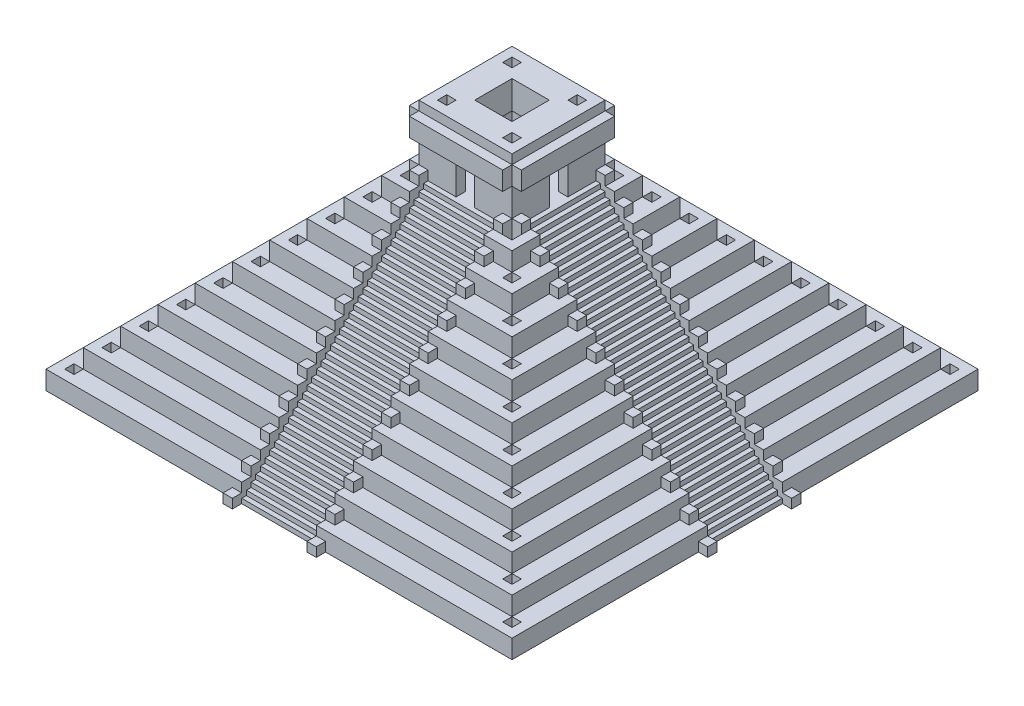
SolidWorks part; units mm, degrees
ref_plane "Ebene vorne" through (0, 0, 0) normal (0, 0, 1) x (1, 0, 0)
ref_plane "Ebene oben" through (0, 0, 0) normal (0, 1, 0) x (1, 0, 0)
ref_plane "Ebene rechts" through (0, 0, 0) normal (1, 0, 0) x (0, 0, -1)
ref_axis "Achse1" through (0, -1.35, 0) along (0, 1, 0)
sketch "Skizze1" plane through (0, 0, 0) normal (0, 1, 0) x (1, 0, 0)
  line L1 (-25, -25) -> (25, -25)
  line L2 (-25, -25) -> (-25, 25)
  line L3 (-25, 25) -> (25, 25)
  line L4 (25, -25) -> (25, 25)
  line L5 (-25, -25) -> (25, 25) construction
  line L6 (-25, 25) -> (25, -25) construction
  line L7 (-20, 20) -> (20, 20)
  line L8 (-20, 20) -> (-20, -20)
  line L9 (-20, -20) -> (20, -20)
  line L10 (20, 20) -> (20, -20)
  dimension "D1" = 50
  dimension "D2" = 5
extrude "Aufsatz-Linear austragen1" add sketch "Skizze1" along normal blind 2
sketch "Skizze2" plane through (0, 2, 0) normal (0, 1, 0) x (1, 0, 0)
  line L8 (-23, -23) -> (23, -23)
  line L9 (23, -23) -> (23, 23)
  line L10 (23, 23) -> (-23, 23)
  line L11 (-23, 23) -> (-23, -23)
  line L12 (-23, -23) -> (23, -23)
  line L13 (23, -23) -> (23, 23)
  line L14 (23, 23) -> (-23, 23)
  line L15 (-23, 23) -> (-23, -23)
  line L20 (18, -18) -> (18, 18)
  line L21 (-18, -18) -> (18, -18)
  line L22 (18, 18) -> (-18, 18)
  line L23 (-18, 18) -> (-18, -18)
  line L24 (18, -18) -> (18, 18)
  line L25 (-18, -18) -> (18, -18)
  line L26 (18, 18) -> (-18, 18)
  line L27 (-18, 18) -> (-18, -18)
  dimension "D1" = 2
  dimension "D2" = 2
extrude "Aufsatz-Linear austragen2" add sketch "Skizze2" along normal blind 2
sketch "Skizze3" plane through (0, 4, 0) normal (0, 1, 0) x (1, 0, 0)
  line L8 (-21, 21) -> (-21, -21)
  line L9 (-21, -21) -> (21, -21)
  line L10 (21, -21) -> (21, 21)
  line L11 (21, 21) -> (-21, 21)
  line L12 (-21, 21) -> (-21, -21)
  line L13 (-21, -21) -> (21, -21)
  line L14 (21, -21) -> (21, 21)
  line L15 (21, 21) -> (-21, 21)
  line L20 (-16, -16) -> (16, -16)
  line L21 (16, -16) -> (16, 16)
  line L22 (16, 16) -> (-16, 16)
  line L23 (-16, 16) -> (-16, -16)
  line L24 (-16, -16) -> (16, -16)
  line L25 (16, -16) -> (16, 16)
  line L26 (16, 16) -> (-16, 16)
  line L27 (-16, 16) -> (-16, -16)
  dimension "D1" = 2
  dimension "D2" = 2
extrude "Aufsatz-Linear austragen3" add sketch "Skizze3" along normal blind 2
sketch "Skizze4" plane through (0, 6, 0) normal (0, 1, 0) x (1, 0, 0)
  line L8 (19, 19) -> (-19, 19)
  line L9 (-19, 19) -> (-19, -19)
  line L10 (-19, -19) -> (19, -19)
  line L11 (19, -19) -> (19, 19)
  line L12 (19, 19) -> (-19, 19)
  line L13 (-19, 19) -> (-19, -19)
  line L14 (-19, -19) -> (19, -19)
  line L15 (19, -19) -> (19, 19)
  line L20 (14, -14) -> (14, 14)
  line L21 (-14, -14) -> (14, -14)
  line L22 (14, 14) -> (-14, 14)
  line L23 (-14, 14) -> (-14, -14)
  line L24 (14, -14) -> (14, 14)
  line L25 (-14, -14) -> (14, -14)
  line L26 (14, 14) -> (-14, 14)
  line L27 (-14, 14) -> (-14, -14)
  dimension "D1" = 2
  dimension "D2" = 2
extrude "Aufsatz-Linear austragen4" add sketch "Skizze4" along normal blind 2
sketch "Skizze5" plane through (0, 8, 0) normal (0, 1, 0) x (1, 0, 0)
  line L8 (17, -17) -> (17, 17)
  line L9 (17, 17) -> (-17, 17)
  line L10 (-17, 17) -> (-17, -17)
  line L11 (-17, -17) -> (17, -17)
  line L12 (17, -17) -> (17, 17)
  line L13 (17, 17) -> (-17, 17)
  line L14 (-17, 17) -> (-17, -17)
  line L15 (-17, -17) -> (17, -17)
  line L20 (-12, -12) -> (12, -12)
  line L21 (12, -12) -> (12, 12)
  line L22 (12, 12) -> (-12, 12)
  line L23 (-12, 12) -> (-12, -12)
  line L24 (-12, -12) -> (12, -12)
  line L25 (12, -12) -> (12, 12)
  line L26 (12, 12) -> (-12, 12)
  line L27 (-12, 12) -> (-12, -12)
  dimension "D1" = 2
  dimension "D2" = 2
extrude "Aufsatz-Linear austragen5" add sketch "Skizze5" along normal blind 2
sketch "Skizze6" plane through (0, 10, 0) normal (0, 1, 0) x (1, 0, 0)
  line L8 (-15, -15) -> (15, -15)
  line L9 (15, -15) -> (15, 15)
  line L10 (15, 15) -> (-15, 15)
  line L11 (-15, 15) -> (-15, -15)
  line L12 (-15, -15) -> (15, -15)
  line L13 (15, -15) -> (15, 15)
  line L14 (15, 15) -> (-15, 15)
  line L15 (-15, 15) -> (-15, -15)
  line L20 (-10, -10) -> (10, -10)
  line L21 (10, -10) -> (10, 10)
  line L22 (10, 10) -> (-10, 10)
  line L23 (-10, 10) -> (-10, -10)
  line L24 (-10, -10) -> (10, -10)
  line L25 (10, -10) -> (10, 10)
  line L26 (10, 10) -> (-10, 10)
  line L27 (-10, 10) -> (-10, -10)
  dimension "D1" = 2
  dimension "D2" = 2
extrude "Aufsatz-Linear austragen6" add sketch "Skizze6" along normal blind 2
sketch "Skizze7" plane through (0, 12, 0) normal (0, 1, 0) x (1, 0, 0)
  line L8 (-13, 13) -> (-13, -13)
  line L9 (-13, -13) -> (13, -13)
  line L10 (13, -13) -> (13, 13)
  line L11 (13, 13) -> (-13, 13)
  line L12 (-13, 13) -> (-13, -13)
  line L13 (-13, -13) -> (13, -13)
  line L14 (13, -13) -> (13, 13)
  line L15 (13, 13) -> (-13, 13)
  line L20 (8, -8) -> (8, 8)
  line L21 (-8, -8) -> (8, -8)
  line L22 (8, 8) -> (-8, 8)
  line L23 (-8, 8) -> (-8, -8)
  line L24 (8, -8) -> (8, 8)
  line L25 (-8, -8) -> (8, -8)
  line L26 (8, 8) -> (-8, 8)
  line L27 (-8, 8) -> (-8, -8)
  dimension "D1" = 2
  dimension "D2" = 2
extrude "Aufsatz-Linear austragen7" add sketch "Skizze7" along normal blind 2
sketch "Skizze8" plane through (0, 14, 0) normal (0, 1, 0) x (1, 0, 0)
  line L8 (11, 11) -> (-11, 11)
  line L9 (-11, 11) -> (-11, -11)
  line L10 (-11, -11) -> (11, -11)
  line L11 (11, -11) -> (11, 11)
  line L12 (11, 11) -> (-11, 11)
  line L13 (-11, 11) -> (-11, -11)
  line L14 (-11, -11) -> (11, -11)
  line L15 (11, -11) -> (11, 11)
  line L20 (6, -6) -> (6, 6)
  line L21 (-6, -6) -> (6, -6)
  line L22 (6, 6) -> (-6, 6)
  line L23 (-6, 6) -> (-6, -6)
  line L24 (6, -6) -> (6, 6)
  line L25 (-6, -6) -> (6, -6)
  line L26 (6, 6) -> (-6, 6)
  line L27 (-6, 6) -> (-6, -6)
  dimension "D1" = 2
  dimension "D2" = 2
extrude "Aufsatz-Linear austragen8" add sketch "Skizze8" along normal blind 2
sketch "Skizze9" plane through (0, 16, 0) normal (0, 1, 0) x (1, 0, 0)
  line L8 (9, -9) -> (9, 9)
  line L9 (9, 9) -> (-9, 9)
  line L10 (-9, 9) -> (-9, -9)
  line L11 (-9, -9) -> (9, -9)
  line L12 (9, -9) -> (9, 9)
  line L13 (9, 9) -> (-9, 9)
  line L14 (-9, 9) -> (-9, -9)
  line L15 (-9, -9) -> (9, -9)
  line L20 (4, -4) -> (4, 4)
  line L21 (-4, -4) -> (4, -4)
  line L22 (-4, 4) -> (-4, -4)
  line L23 (4, 4) -> (-4, 4)
  line L24 (4, -4) -> (4, 4)
  line L25 (-4, -4) -> (4, -4)
  line L26 (-4, 4) -> (-4, -4)
  line L27 (4, 4) -> (-4, 4)
  dimension "D1" = 2
  dimension "D2" = 2
extrude "Aufsatz-Linear austragen9" add sketch "Skizze9" along normal blind 2
sketch "Skizze10" plane through (0, 18, 0) normal (0, 1, 0) x (1, 0, 0)
  line L8 (-7, -7) -> (7, -7)
  line L9 (7, -7) -> (7, 7)
  line L10 (7, 7) -> (-7, 7)
  line L11 (-7, 7) -> (-7, -7)
  line L12 (-7, -7) -> (7, -7)
  line L13 (7, -7) -> (7, 7)
  line L14 (7, 7) -> (-7, 7)
  line L15 (-7, 7) -> (-7, -7)
  line L20 (-2, -2) -> (2, -2)
  line L21 (2, -2) -> (2, 2)
  line L22 (2, 2) -> (-2, 2)
  line L23 (-2, 2) -> (-2, -2)
  line L24 (-2, -2) -> (2, -2)
  line L25 (2, -2) -> (2, 2)
  line L26 (2, 2) -> (-2, 2)
  line L27 (-2, 2) -> (-2, -2)
  dimension "D1" = 2
  dimension "D2" = 2
extrude "Aufsatz-Linear austragen10" add sketch "Skizze10" along normal blind 2
sketch "Skizze12" plane through (0, 20, 0) normal (0, 1, 0) x (1, 0, 0)
  line L4 (4, 4) -> (-4, 4)
  line L5 (-4, 4) -> (-4, -4)
  line L6 (-4, -4) -> (4, -4)
  line L7 (4, -4) -> (4, 4)
  line L8 (-5, 5) -> (-5, -5)
  line L9 (-5, -5) -> (5, -5)
  line L10 (5, -5) -> (5, 5)
  line L11 (5, 5) -> (-5, 5)
  line L12 (-5, 5) -> (-5, -5)
  line L13 (-5, -5) -> (5, -5)
  line L14 (5, -5) -> (5, 5)
  line L15 (5, 5) -> (-5, 5)
  line L16 (-5, 1) -> (-4, 1)
  line L17 (-1, 5) -> (-1, 4)
  line L18 (-5, 5) -> (4, -4) construction
  line L19 (0, 5) -> (0, -5) construction
  line L20 (5, 1) -> (4, 1)
  line L21 (1, 5) -> (1, 4)
  line L22 (-1, -5) -> (-1, -4)
  line L23 (-5, -1) -> (-4, -1)
  line L24 (5, -1) -> (4, -1)
  line L25 (1, -5) -> (1, -4)
  dimension "D3" = 2
  dimension "D1" = 2
  dimension "D2" = 1
extrude "Aufsatz-Linear austragen11" add sketch "Skizze12" along normal blind 4 contours L17 L15 L12 L16 L5 L4 | L15 L21 L4 L7 L20 L14 | L25 L13 L14 L24 L7 L6 | L23 L12 L13 L22 L6 L5 region at (2.5, 20, -4.0566) region at (-2.5, 20, -4.0566) region at (4.5, 20, 1.0566) region at (-4.0566, 20, 2.5)
sketch "Skizze13" plane through (0, 24, 0) normal (0, 1, 0) x (1, 0, 0)
  line L0 (-2, 2) -> (-2, -2) construction
  line L1 (-6, 6) -> (6, 6)
  line L2 (-5, 5) -> (5, 5)
  line L3 (-5, 5) -> (-5, -5)
  line L4 (-5, -5) -> (5, -5)
  line L5 (2, 2) -> (-2, 2) construction
  line L6 (2, -2) -> (2, 2) construction
  line L8 (5, 5) -> (5, -5)
  line L9 (6, 6) -> (6, -6)
  line L10 (-6, -6) -> (6, -6)
  line L11 (-6, 6) -> (-6, -6)
  line L24 (-2, 2) -> (-2, -2)
  line L25 (2, 2) -> (-2, 2)
  line L26 (2, -2) -> (2, 2)
  line L27 (-2, -2) -> (2, -2)
  line M1 (-1, 4) -> (-1, 5)
  line M2 (-1, 5) -> (-5, 5)
  line M3 (-5, 5) -> (-5, 1)
  line M4 (-5, 1) -> (-4, 1)
  line M5 (-4, 1) -> (-4, 4)
  line M6 (-4, 4) -> (-1, 4)
  dimension "D1" = 1
extrude "Aufsatz-Linear austragen12" add sketch "Skizze13" along normal blind 2 contours L1 L11 L10 L9 L2 L8 L4 L3 M3 M2 | M6 M1 M2 M3 M4 M5 | L8 L2 L3 L4 L27 L24 L25 L26 M1 M6 M5 M4 region at (0, 24, -5.8303) region at (-3, 24, -4.9434) region at (2, 24, -4.8586)
extrude "Aufsatz-Linear austragen13" add sketch "Skizze13<3>" along normal blind 3 contours L8 L2 L3 L4 L27 L24 L25 L26 M1 M6 M5 M4 | M6 M1 M2 M3 M4 M5 region at (-3, 24, -4.9434) region at (2, 24, -4.8586)
sketch "Skizze13<3>" plane through (0, 24, 0) normal (0, 1, 0) x (1, 0, 0) same geometry as "Skizze13"
sketch "Skizze11" plane through (0, 27, 0) normal (0, 1, 0) x (1, 0, 0)
  line L0 (2, 2) -> (-2, 2) construction
  line L1 (-23, 23) -> (-24, 23)
  line L2 (-23, 23) -> (-23, 24)
  line L3 (-23, 24) -> (-24, 24)
  line L4 (-24, 23) -> (-24, 24)
  line L5 (-21, 21) -> (-22, 21)
  line L6 (-21, 21) -> (-21, 22)
  line L7 (-21, 22) -> (-22, 22)
  line L8 (-22, 21) -> (-22, 22)
  line L9 (-19, 19) -> (-20, 19)
  line L10 (-19, 19) -> (-19, 20)
  line L11 (-19, 20) -> (-20, 20)
  line L12 (-20, 19) -> (-20, 20)
  line L13 (-17, 17) -> (-18, 17)
  line L14 (-17, 17) -> (-17, 18)
  line L15 (-17, 18) -> (-18, 18)
  line L16 (-18, 17) -> (-18, 18)
  line L17 (-15, 15) -> (-16, 15)
  line L18 (-15, 15) -> (-15, 16)
  line L19 (-15, 16) -> (-16, 16)
  line L20 (-16, 15) -> (-16, 16)
  line L21 (-13, 13) -> (-14, 13)
  line L22 (-13, 13) -> (-13, 14)
  line L23 (-13, 14) -> (-14, 14)
  line L24 (-14, 13) -> (-14, 14)
  line L25 (-11, 11) -> (-12, 11)
  line L26 (-11, 11) -> (-11, 12)
  line L27 (-11, 12) -> (-12, 12)
  line L28 (-12, 11) -> (-12, 12)
  line L29 (-9, 9) -> (-10, 9)
  line L30 (-9, 9) -> (-9, 10)
  line L31 (-9, 10) -> (-10, 10)
  line L32 (-10, 9) -> (-10, 10)
  line L33 (-7, 7) -> (-8, 7)
  line L34 (-7, 7) -> (-7, 8)
  line L35 (-7, 8) -> (-8, 8)
  line L36 (-8, 7) -> (-8, 8)
  line L37 (-6, 6) -> (-5, 6)
  line L38 (-6, 6) -> (-6, 5)
  line L39 (-6, 5) -> (-5, 5)
  line L40 (-5, 6) -> (-5, 5)
  line L41 (-4, 4) -> (-3, 4)
  line L42 (-4, 4) -> (-4, 3)
  line L43 (-4, 3) -> (-3, 3)
  line L44 (-3, 4) -> (-3, 3)
  line L45 (-2, 2) -> (-2, -2) construction
  dimension "D1" = 1
  dimension "D2" = 1
  dimension "D3" = 1
extrude "Schnitt-Linear austragen1" cut sketch "Skizze11" against normal through all
sketch "Skizze14" plane through (0, 0, 0) normal (0, 0, 1) x (1, 0, 0)
  line L0 (-5, 24) -> (-5, 20) construction
  line L1 (-6, 20) -> (-5, 20)
  line L2 (-6, 20) -> (-6, 21)
  line L3 (-6, 21) -> (-5, 21)
  line L4 (-5, 20) -> (-5, 21)
  line L5 (-7, 20) -> (-7, 18) construction
  line L6 (-8, 18) -> (-7, 18)
  line L7 (-8, 18) -> (-8, 19)
  line L8 (-8, 19) -> (-7, 19)
  line L9 (-7, 18) -> (-7, 19)
  line L10 (-9, 18) -> (-9, 16) construction
  line L11 (-10, 16) -> (-9, 16)
  line L12 (-10, 16) -> (-10, 17)
  line L13 (-10, 17) -> (-9, 17)
  line L14 (-9, 16) -> (-9, 17)
  line L15 (-11, 16) -> (-11, 14) construction
  line L16 (-12, 14) -> (-11, 14)
  line L17 (-12, 14) -> (-12, 15)
  line L18 (-12, 15) -> (-11, 15)
  line L19 (-11, 14) -> (-11, 15)
  line L20 (-13, 14) -> (-13, 12) construction
  line L21 (-14, 12) -> (-13, 12)
  line L22 (-14, 12) -> (-14, 13)
  line L23 (-14, 13) -> (-13, 13)
  line L24 (-13, 12) -> (-13, 13)
  line L25 (-15, 12) -> (-15, 10) construction
  line L26 (-16, 10) -> (-15, 10)
  line L27 (-16, 10) -> (-16, 11)
  line L28 (-16, 11) -> (-15, 11)
  line L29 (-15, 10) -> (-15, 11)
  line L30 (-17, 10) -> (-17, 8) construction
  line L31 (-18, 8) -> (-17, 8)
  line L32 (-18, 8) -> (-18, 9)
  line L33 (-18, 9) -> (-17, 9)
  line L34 (-17, 8) -> (-17, 9)
  line L35 (-19, 8) -> (-19, 6) construction
  line L36 (-20, 6) -> (-19, 6)
  line L37 (-20, 6) -> (-20, 7)
  line L38 (-20, 7) -> (-19, 7)
  line L39 (-19, 6) -> (-19, 7)
  line L40 (-21, 6) -> (-21, 4) construction
  line L41 (-22, 4) -> (-21, 4)
  line L42 (-22, 4) -> (-22, 5)
  line L43 (-22, 5) -> (-21, 5)
  line L44 (-21, 4) -> (-21, 5)
  line L45 (-23, 4) -> (-23, 2) construction
  line L46 (-24, 2) -> (-23, 2)
  line L47 (-24, 2) -> (-24, 3)
  line L48 (-24, 3) -> (-23, 3)
  line L49 (-23, 2) -> (-23, 3)
  line L50 (-25, 2) -> (-25, 0) construction
  line L51 (-25, 1) -> (-26, 1)
  line L52 (-25, 1) -> (-25, 0)
  line L53 (-25, 0) -> (-26, 0)
  line L54 (-26, 1) -> (-26, 0)
extrude "Aufsatz-Linear austragen14" add sketch "Skizze14" along normal blind 1 from offset 4
mirror "Spiegeln1" about plane through (0, 0, 0) normal (0, 0, 1) of "Aufsatz-Linear austragen14"
sketch "Skizze15" plane through (0, 0, 0) normal (0, 0, 1) x (1, 0, 0)
  line L0 (-25, 0) -> (-25, 0.5)
  line L1 (-25, 0) -> (-25, 1) construction
  line L2 (-25, 0.5) -> (-24.5, 0.5)
  line L3 (-24.5, 1) -> (-24, 1)
  line L4 (-24.5, 0.5) -> (-24.5, 1)
  line L5 (-24, 1.5) -> (-23.5, 1.5)
  line L6 (-24, 1) -> (-24, 1.5)
  line L7 (-23.5, 2) -> (-23, 2)
  line L8 (-23.5, 1.5) -> (-23.5, 2)
  line L9 (-23, 2.5) -> (-22.5, 2.5)
  line L10 (-23, 2) -> (-23, 2.5)
  line L11 (-22.5, 3) -> (-22, 3)
  line L12 (-22.5, 2.5) -> (-22.5, 3)
  line L13 (-22, 3.5) -> (-21.5, 3.5)
  line L14 (-22, 3) -> (-22, 3.5)
  line L15 (-21.5, 4) -> (-21, 4)
  line L16 (-21.5, 3.5) -> (-21.5, 4)
  line L17 (-21, 4.5) -> (-20.5, 4.5)
  line L18 (-21, 4) -> (-21, 4.5)
  line L19 (-20.5, 5) -> (-20, 5)
  line L20 (-20.5, 4.5) -> (-20.5, 5)
  line L21 (-20, 5.5) -> (-19.5, 5.5)
  line L22 (-20, 5) -> (-20, 5.5)
  line L23 (-19.5, 6) -> (-19, 6)
  line L24 (-19.5, 5.5) -> (-19.5, 6)
  line L25 (-19, 6.5) -> (-18.5, 6.5)
  line L26 (-19, 6) -> (-19, 6.5)
  line L27 (-18.5, 7) -> (-18, 7)
  line L28 (-18.5, 6.5) -> (-18.5, 7)
  line L29 (-18, 7.5) -> (-17.5, 7.5)
  line L30 (-18, 7) -> (-18, 7.5)
  line L31 (-17.5, 8) -> (-17, 8)
  line L32 (-17.5, 7.5) -> (-17.5, 8)
  line L33 (-17, 8.5) -> (-16.5, 8.5)
  line L34 (-17, 8) -> (-17, 8.5)
  line L35 (-16.5, 9) -> (-16, 9)
  line L36 (-16.5, 8.5) -> (-16.5, 9)
  line L37 (-16, 9.5) -> (-15.5, 9.5)
  line L38 (-16, 9) -> (-16, 9.5)
  line L39 (-15.5, 10) -> (-15, 10)
  line L40 (-15.5, 9.5) -> (-15.5, 10)
  line L41 (-15, 10.5) -> (-14.5, 10.5)
  line L42 (-15, 10) -> (-15, 10.5)
  line L43 (-14.5, 11) -> (-14, 11)
  line L44 (-14.5, 10.5) -> (-14.5, 11)
  line L45 (-14, 11.5) -> (-13.5, 11.5)
  line L46 (-14, 11) -> (-14, 11.5)
  line L47 (-13.5, 12) -> (-13, 12)
  line L48 (-13.5, 11.5) -> (-13.5, 12)
  line L49 (-13, 12.5) -> (-12.5, 12.5)
  line L50 (-13, 12) -> (-13, 12.5)
  line L51 (-12.5, 13) -> (-12, 13)
  line L52 (-12.5, 12.5) -> (-12.5, 13)
  line L53 (-12, 13.5) -> (-11.5, 13.5)
  line L54 (-12, 13) -> (-12, 13.5)
  line L55 (-11.5, 14) -> (-11, 14)
  line L56 (-11.5, 13.5) -> (-11.5, 14)
  line L57 (-11, 14.5) -> (-10.5, 14.5)
  line L58 (-11, 14) -> (-11, 14.5)
  line L59 (-10.5, 15) -> (-10, 15)
  line L60 (-10.5, 14.5) -> (-10.5, 15)
  line L61 (-10, 15.5) -> (-9.5, 15.5)
  line L62 (-10, 15) -> (-10, 15.5)
  line L63 (-9.5, 16) -> (-9, 16)
  line L64 (-9.5, 15.5) -> (-9.5, 16)
  line L65 (-9, 16.5) -> (-8.5, 16.5)
  line L66 (-9, 16) -> (-9, 16.5)
  line L67 (-8.5, 17) -> (-8, 17)
  line L68 (-8.5, 16.5) -> (-8.5, 17)
  line L69 (-8, 17.5) -> (-7.5, 17.5)
  line L70 (-8, 17) -> (-8, 17.5)
  line L71 (-7.5, 18) -> (-7, 18)
  line L72 (-7.5, 17.5) -> (-7.5, 18)
  line L73 (-7, 18.5) -> (-6.5, 18.5)
  line L74 (-7, 18) -> (-7, 18.5)
  line L75 (-6.5, 19) -> (-6, 19)
  line L76 (-6.5, 18.5) -> (-6.5, 19)
  line L77 (-6, 19.5) -> (-5.5, 19.5)
  line L78 (-6, 19) -> (-6, 19.5)
  line L79 (-5.5, 20) -> (-5, 20)
  line L80 (-5.5, 19.5) -> (-5.5, 20)
  line L81 (-5, 20) -> (-5, 24)
  line L82 (-5, 24) -> (-26, 24)
  line L83 (-26, 24) -> (-26, 0)
  line L84 (-26, 0) -> (-25, 0)
  dimension "D1" = 40
extrude "Schnitt-Linear austragen2" cut sketch "Skizze15" against normal mid plane 8
pattern_circular "Kreismuster1" count 4 over 360 about axis through (0, -1.35, 0) along (0, 1, 0) of "Schnitt-Linear austragen1", "Aufsatz-Linear austragen14", "Spiegeln1", "Schnitt-Linear austragen2"
